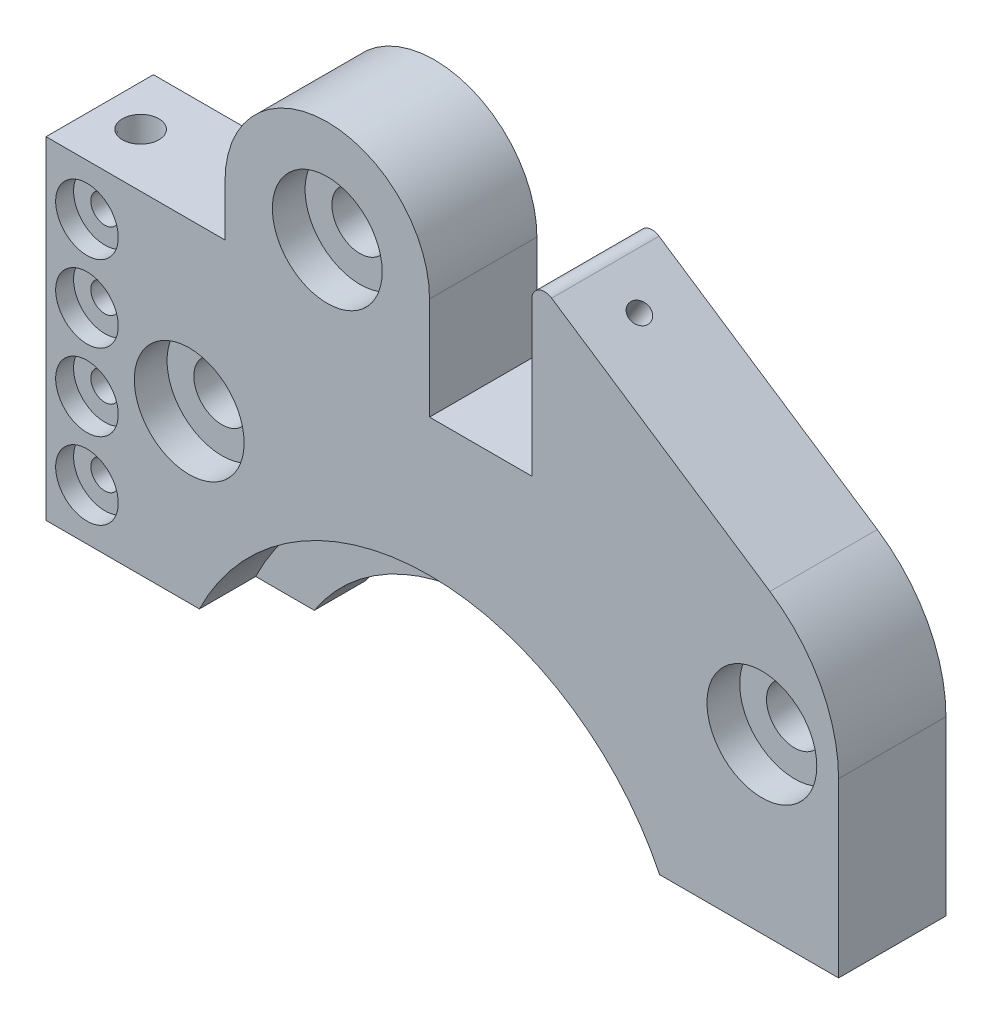
SolidWorks part; units mm, degrees
ref_plane "Front Plane" through (0, 0, 0) normal (0, 0, 1) x (1, 0, 0)
ref_plane "Top Plane" through (0, 0, 0) normal (0, 1, 0) x (1, 0, 0)
ref_plane "Right Plane" through (0, 0, 0) normal (1, 0, 0) x (0, 0, -1)
sketch "Sketch1" plane through (0, 0, 0) normal (0, 0, 1) x (1, 0, 0)
  line L0 (35, 65) -> (0, 65)
  line L1 (0, 65) -> (0, 0)
  line L2 (0, 0) -> (30, 0)
  line L3 (30, 0) -> (120, 0) construction
  line L4 (120, 0) -> (155, 0)
  line L5 (155, 0) -> (155, 33.7586)
  line L6 (141.5831, 58.7586) -> (98.8819, 87.0833)
  line L7 (95, 85) -> (95, 55)
  line L8 (95, 55) -> (75, 55)
  line L9 (75, 55) -> (75, 75)
  line L11 (35, 75) -> (35, 65)
  line L12 (75, -21.7945) -> (75, 40.8014) construction
  line L13 (0, 32.5) -> (43.179, 32.5) construction
  arc A0 (30, 0) -> (120, 0) centre (75, -21.7945) cw
  arc A1 (41.459, 0) -> (108.541, 0) centre (75, -21.7945) cw construction
  arc A2 (35, 75) -> (75, 75) centre (55, 75) cw
  arc A3 (155, 33.7586) -> (141.5831, 58.7586) centre (125, 33.7586) ccw
  arc A4 (98.8819, 87.0833) -> (95, 85) centre (97.5, 85) ccw
  arc A5 (39, -4.3589) -> (111, -4.3589) centre (75, -21.7945) cw construction
  circle A6 centre (8, 10) radius 5 construction
  circle A7 centre (8, 25) radius 5 construction
  circle A8 centre (8, 40) radius 5 construction
  circle A9 centre (8, 55) radius 5 construction
  circle A10 centre (28, 32.5) radius 10 construction
  circle A11 centre (140, 33.7586) radius 7.5 construction
  point P17 (75, 28.2055)
  point P23 (75, 9.5034)
  dimension "D1" = 30
  dimension "D2" = 2.5
  dimension "D4" = 20
  dimension "D5" = 50
  dimension "D6" = 45
  dimension "D13" = 10
  dimension "D17" = 10
  dimension "D21" = 20
  dimension "D23" = 15
  dimension "D3" = 65
  dimension "D7" = 30
  dimension "D8" = 35
  dimension "D9" = 10
  dimension "D10" = 20
  dimension "D11" = 30
  dimension "D12" = 20
  dimension "D14" = 35
  dimension "D15" = 25
  dimension "D16" = 10
  dimension "D18" = 8
  dimension "D20" = 15
  dimension "D22" = 28
  dimension "D24" = 15
  dimension "D19" = 4
extrude "Boss-Extrude1" add sketch "Sketch1" along normal blind 21
sketch "Sketch2" plane through (0, 0, 0) normal (0, 0, 1) x (1, 0, 0)
  line L0 (30, 0) -> (41.459, 0)
  line L1 (108.541, 0) -> (120, 0)
  arc A0 (108.541, 0) -> (41.459, 0) centre (75, -21.7945) ccw construction
  arc A1 (108.541, 0) -> (41.459, 0) centre (75, -21.7945) ccw
  arc A2 (120, 0) -> (30, 0) centre (75, -21.7945) ccw construction
  arc A3 (120, 0) -> (30, 0) centre (75, -21.7945) ccw
extrude "Boss-Extrude2" add sketch "Sketch2" along normal blind 10
sketch "Sketch8" plane through (0, 65, 0) normal (0, 1, 0) x (1, 0, 0)
  line L0 (0, -21) -> (0, 0) construction
  line L1 (0, -10.5) -> (24.3066, -10.5) construction
  circle A0 centre (8, -10.5) radius 2.5 construction
  dimension "D2" = 5
  dimension "D1" = 8
hole_wizard "1/16 Rc Tapped Hole1" positions "Sketch15" profile "Sketch16" size "1/16" standard "ISO" end condition up to next
sketch "Sketch15" plane through (0, 65, 0) normal (0, 1, 0) x (1, 0, 0)
  point P0 (8, -10.5)
sketch "Sketch16" plane through (8, 65, 10.5) normal (1, 0, 0) x (0, 0, 1)
  line L0 (0, 0) -> (0, 65)
  line L1 (0, 65) -> (3.05, 65)
  line L2 (-3.34, 7.4) -> (-3.571, 0) construction
  line L3 (3.05, 65) -> (3.05, 7.4)
  line L4 (3.05, 7.4) -> (3.34, 7.4)
  line L5 (3.34, 7.4) -> (3.571, 0)
  line L7 (3.571, 0) -> (0, 0)
  line L8 (0, -6.35) -> (0, 107.95) construction
  line L11 (-3.05, 7.4) -> (-3.34, 7.4) construction
  dimension "Thru Tap Drill Dia." = 6.1
  dimension "Thru Tap Drill Depth" = 65
  dimension "Thread Dia." = 7.142
  dimension "Thread Angle" = 3.576
  dimension "Thread Depth" = 7.4
cosmetic thread "Hole Thread1" parameters "D1"=7.4, "D2"=7.723
hole_wizard "CBORE for M5 Hex Head Bolt1" positions "Sketch3" profile "Sketch4" counterbore size "M5" standard "ISO" end condition up to next
sketch "Sketch3" plane through (0, 0, 21) normal (0, 0, 1) x (1, 0, 0)
  point P0 (8, 55)
  point P3 (8, 40)
  point P6 (8, 25)
  point P9 (8, 10)
sketch "Sketch4" plane through (8, 55, 21) normal (1, 0, 0) x (0, -1, 0)
  line L0 (0, 0) -> (0, 7.45)
  line L1 (0, 7.45) -> (2.75, 7.45)
  line L3 (2.75, 7.45) -> (2.75, 3.5)
  line L4 (2.75, 3.5) -> (6.119, 3.5)
  line L5 (6.119, 3.5) -> (6.119, 0)
  line L7 (6.119, 0) -> (0, 0)
  line L11 (0, -6.35) -> (0, 107.95) construction
  dimension "Thru Hole Dia." = 5.5
  dimension "Thru Hole Depth" = 7.45
  dimension "C'Bore Dia." = 12.238
  dimension "C'Bore Depth" = 3.5
hole_wizard "CBORE for M10 Hex Head Bolt1" positions "Sketch5" profile "Sketch6" counterbore size "M10" standard "ISO" end condition up to next
sketch "Sketch5" plane through (0, 0, 21) normal (0, 0, 1) x (1, 0, 0)
  point P0 (28, 32.5)
  point P3 (55, 75)
  point P6 (140, 33.7586)
sketch "Sketch6" plane through (28, 32.5, 21) normal (1, 0, 0) x (0, -1, 0)
  line L0 (0, 0) -> (0, 21)
  line L1 (0, 21) -> (5.5, 21)
  line L3 (5.5, 21) -> (5.5, 6.4)
  line L4 (5.5, 6.4) -> (10.7375, 6.4)
  line L5 (10.7375, 6.4) -> (10.7375, 0)
  line L7 (10.7375, 0) -> (0, 0)
  line L11 (0, -6.35) -> (0, 107.95) construction
  dimension "Thru Hole Dia." = 11
  dimension "Thru Hole Depth" = 21
  dimension "C'Bore Dia." = 21.475
  dimension "C'Bore Depth" = 6.4
sketch "Sketch11" plane through (70.3282, 106.0237, 0) normal (0.5528, 0.8333, 0) x (0.8333, -0.5528, 0)
  line L0 (34.2645, -10.5) -> (85.5059, -10.5) construction
  line L1 (34.2645, -21) -> (34.2645, 0) construction
  line L2 (85.5059, -21) -> (85.5059, 0) construction
  circle A0 centre (42.2645, -10.5) radius 2 construction
  dimension "D1" = 4
  dimension "D2" = 8
hole_wizard "Ø4.0mm Dowel Hole1" positions "Sketch12" profile "Sketch14" hole size "Ø4.0" standard "ISO"
sketch "Sketch12" plane through (70.3282, 106.0237, 0) normal (0.5528, 0.8333, 0) x (0.8333, -0.5528, 0)
  point P0 (42.2645, -10.5)
sketch "Sketch14" plane through (105.5486, 82.6612, 10.5) normal (0, 0, 1) x (-0.8333, 0.5528, 0)
  line L0 (0, 0) -> (0, 11.2017)
  line L1 (0, 11.2017) -> (2, 10)
  line L2 (2, 10) -> (2, 0)
  line L5 (2, 0) -> (0, 0)
  line L10 (0, 11.2017) -> (-2, 10) construction
  line L11 (0, -6.35) -> (0, 107.95) construction
  dimension "Hole Dia." = 4
  dimension "Hole Depth" = 10
  dimension "Drill Angle" = 118
